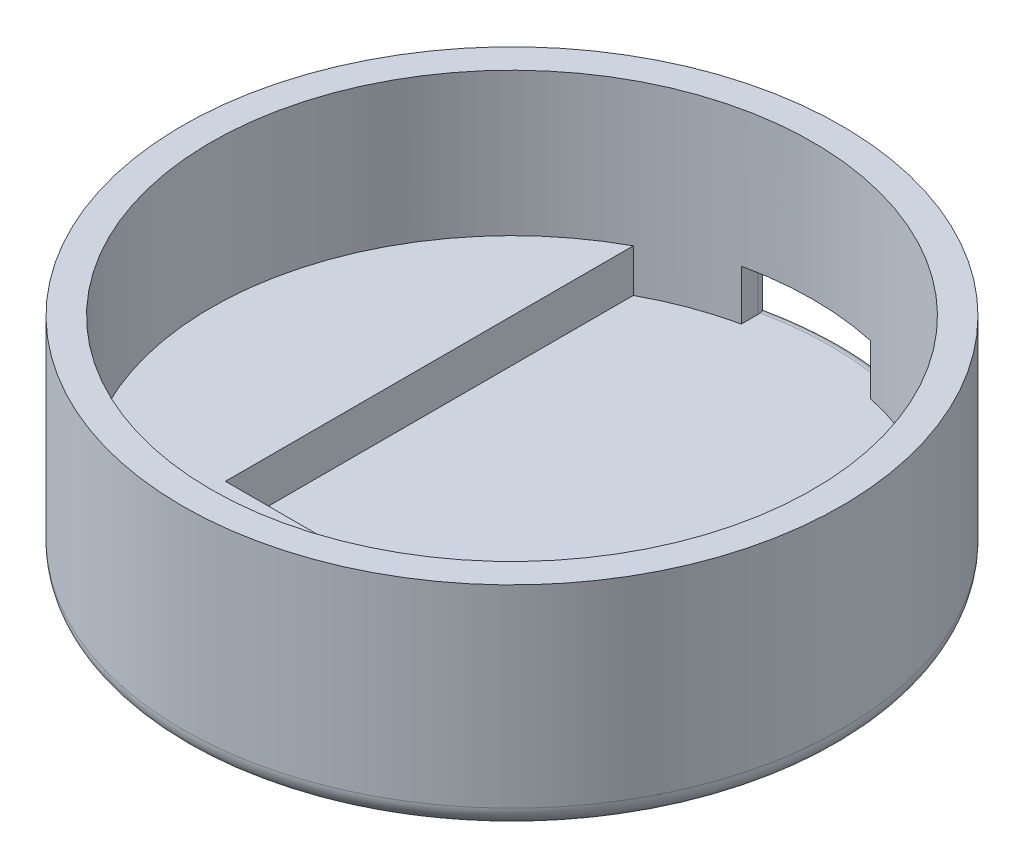
SolidWorks part; units mm, degrees
ref_plane "Front Plane" through (0, 0, 0) normal (0, 0, 1) x (1, 0, 0)
ref_plane "Top Plane" through (0, 0, 0) normal (0, 1, 0) x (1, 0, 0)
ref_plane "Right Plane" through (0, 0, 0) normal (1, 0, 0) x (0, 0, -1)
sketch "Sketch1" plane through (0, 0, 0) normal (0, 1, 0) x (1, 0, 0)
  circle A0 centre (0, 0) radius 23
  dimension "D1" = 46
extrude "Boss-Extrude1" add sketch "Sketch1" along normal blind 15
sketch "Sketch2" plane through (0, 15, 0) normal (0, 1, 0) x (1, 0, 0)
  circle A0 centre (0, 0) radius 21
  circle A1 centre (0, 0) radius 23 construction
  dimension "D1" = 2
extrude "Cut-Extrude1" cut sketch "Sketch2" against normal blind 10
sketch "Sketch3" plane through (0, 5, 0) normal (0, 1, 0) x (1, 0, 0)
  line L0 (0, 0) -> (-21, 0)
  line L1 (0, 0) -> (21, 0)
  line L2 (-10, 0) -> (-10, -10)
  line L3 (-10, -10) -> (10, -10)
  line L4 (10, -10) -> (10, 0)
  line L5 (-10, 0) -> (-10, 18.4662)
  circle A0 centre (0, 0) radius 21
  point P8 (0, -10)
  circle M3 centre (0, 0) radius 21
  dimension "D1" = 42
  dimension "D2" = 10
  dimension "D3" = 20
  dimension "D4" = 0
extrude "Cut-Extrude2" cut sketch "Sketch3" against normal blind 3 contours L0 L1 M3 | L3 L4 L1 L0 L2
sketch "Sketch4" plane through (0, 0, 0) normal (0, 0, 1) x (1, 0, 0)
  line L0 (21, 2) -> (-10, 2) construction
  line L1 (-4.5, 5.5) -> (4.5, 5.5)
  line L2 (-4.5, 5.5) -> (-4.5, 2)
  line L3 (-4.5, 2) -> (4.5, 2)
  line L4 (4.5, 5.5) -> (4.5, 2)
  point P6 (0, 2)
  dimension "D1" = 9
  dimension "D2" = 3.5
  dimension "D3" = 0
extrude "Cut-Extrude3" cut sketch "Sketch4" against normal up to next
fillet "Fillet1" radius 1.5 1 edges at (0, 0, 23)
fillet "Fillet2" radius 0.7 4 edges at (0, 2, -23) (-4.5, 3.75, -22.5555) (0, 5.5, -23) (4.5, 3.75, -22.5555)
